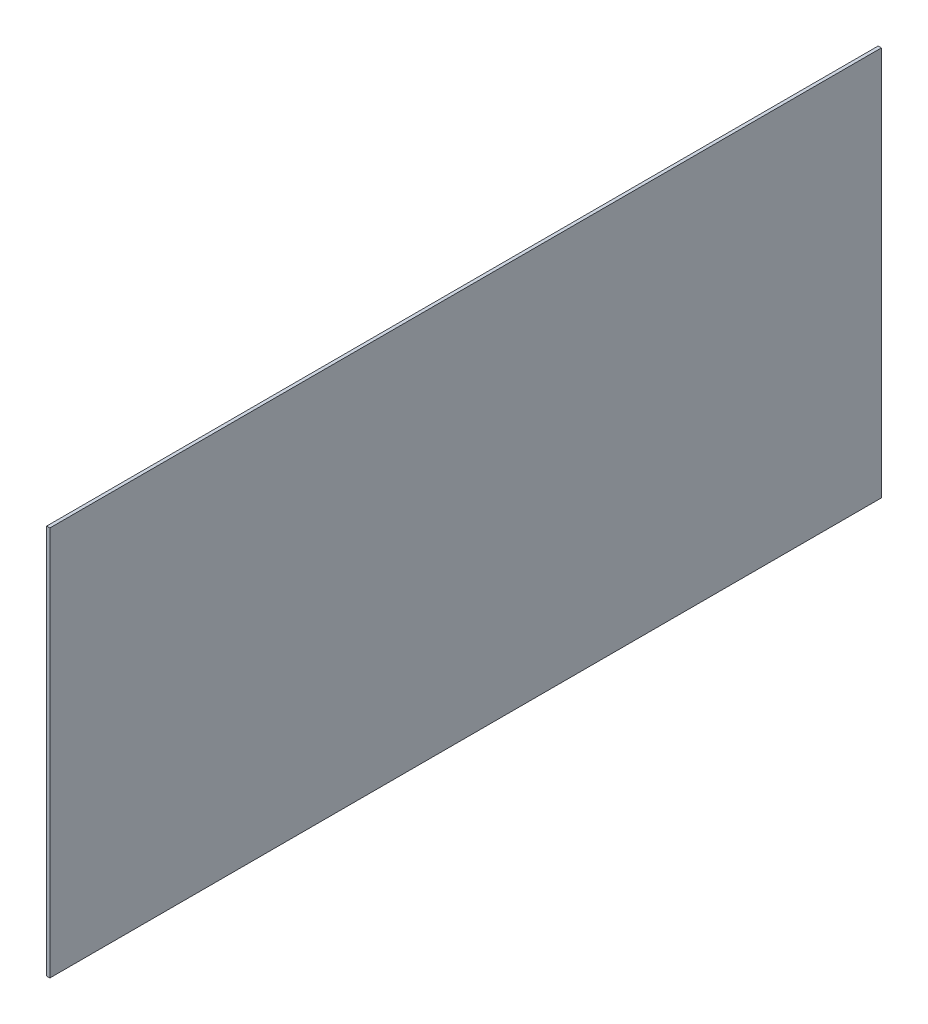
SolidWorks part; units mm, degrees
ref_plane "Front" through (0, 0, 0) normal (0, 0, 1) x (1, 0, 0)
ref_plane "Top" through (0, 0, 0) normal (0, 1, 0) x (1, 0, 0)
ref_plane "Right" through (0, 0, 0) normal (1, 0, 0) x (0, 0, -1)
sketch "Sketch1" plane through (0, 0, 0) normal (0, 1, 0) x (1, 0, 0)
  line L1 (0, 0) -> (6.35, 0)
  line L2 (0, 0) -> (0, -1625.6)
  line L3 (0, -1625.6) -> (6.35, -1625.6)
  line L4 (6.35, 0) -> (6.35, -1625.6)
  dimension "D1" = 6.35
  dimension "D2" = 1625.6
extrude "Boss-Extrude1" add sketch "Sketch1" along normal blind 762
